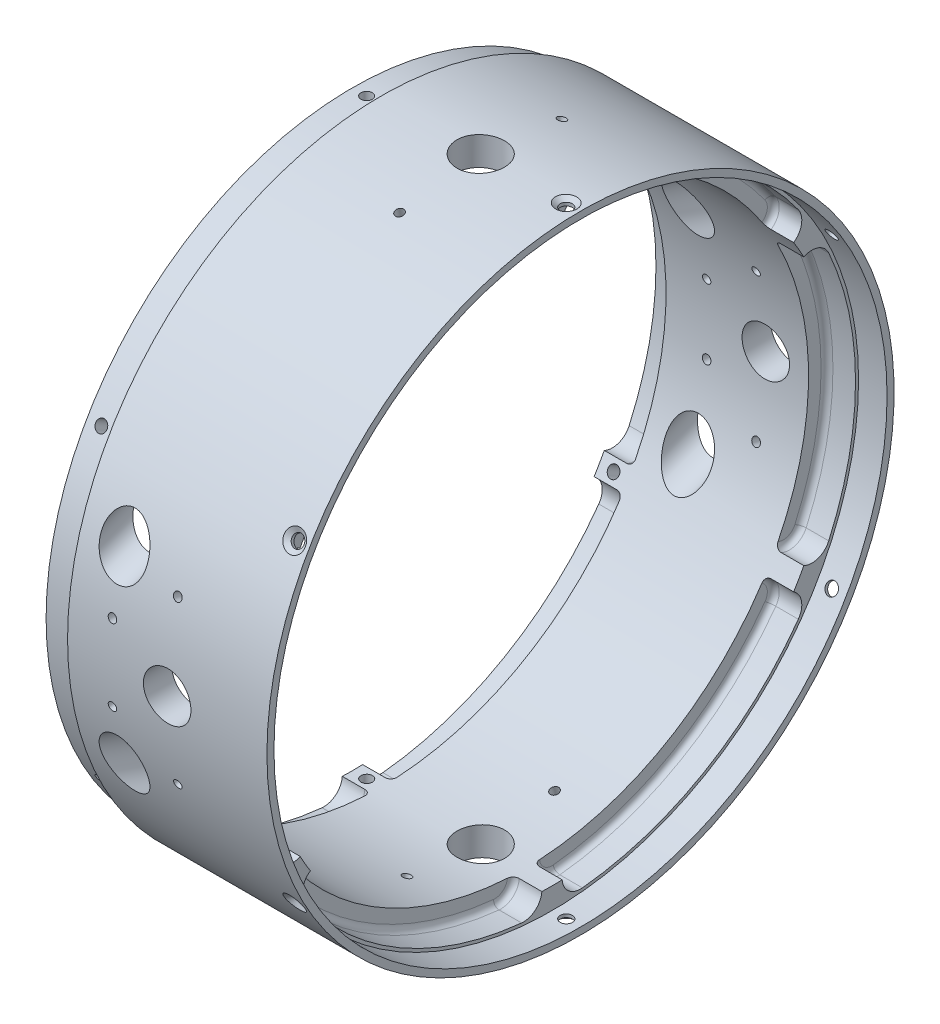
SolidWorks part; units mm, degrees
note: '?' marks a value the reader was unsure of.
material "6061-T6 (SS)"
ref_plane "Front" through (0, 0, 0) normal (0, 0, 1) x (1, 0, 0)
ref_plane "Top" through (0, 0, 0) normal (0, 1, 0) x (1, 0, 0)
ref_plane "Right" through (0, 0, 0) normal (1, 0, 0) x (0, 0, -1)
sketch "Sketch1" plane through (0, 0, 0) normal (0, 0, 1) x (1, 0, 0)
  line L0 (-0.762, 7.62) -> (7.62, 7.62)
  line L1 (-45.6692, 7.62) -> (-0.762, 7.62)
  line L2 (7.62, 7.62) -> (7.62, 5.7404)
  line L3 (0, 0) -> (-53.34, 0)
  line L4 (7.62, 5.7404) -> (0, 5.7404)
  line L5 (-53.34, 5.6896) -> (-53.34, 0)
  line L6 (-45.6692, 7.62) -> (-45.6692, 5.6896)
  line L7 (-45.6692, 5.6896) -> (-53.34, 5.6896)
  line L8 (-51.9562, -76.2) -> (21.757, -76.2) construction
  line L9 (0, 5.7404) -> (0, 0)
  point P1 (-7.62, 0)
  point P4 (-45.72, 0)
  dimension "D1" = 7.6708
  dimension "D2" = 8.382
  dimension "D3" = 1.8796
  dimension "D4" = 7.62
  dimension "D5" = 76.2
  dimension "D6" = 5.6896
  dimension "D7" = 38.1
  dimension "D8" = 83.82
  dimension "D9" = 7.62
  dimension "D10" = 7.62
revolve "Revolve2" add sketch "Sketch1" angle 360 about L8
ref_point "Point1"
ref_plane "Plane1" through (0, -76.2, 0) normal (0, 1, 0) x (1, 0, 0)
ref_plane "Plane2" through (0, -158.0896, 0) normal (0, -1, 0) x (-1, 0, 0)
hole_wizard "#31 (0.12) Diameter Hole1" positions "3DSketch1" profile "Sketch11" hole size "#31" standard "ANSI Inch"
sketch3d "3DSketch1"
  point P0 (-49.53, -158.0896, 0)
  dimension "D1" = 3.81
sketch "Sketch11" plane through (-49.53, -158.0896, 0) normal (1, 0, 0) x (0, 0, -1)
  line L0 (0, 0) -> (0, 185.9821)
  line L1 (0, 185.9821) -> (1.524, 185.9821)
  line L2 (1.524, 185.9821) -> (1.524, 0)
  line L5 (1.524, 0) -> (0, 0)
  line L11 (0, -6.35) -> (0, 107.95) construction
  dimension "Thru Hole Dia." = 3.048
  dimension "Thru Hole Depth" = 185.9821
pattern_circular "CirPattern4" count 6 over 360 of "#31 (0.12) Diameter Hole1"
sketch "Sketch8" plane through (-53.34, 0, 0) normal (-1, 0, 0) x (0, 0, 1)
  line L0 (-7.6343, -152.0166) -> (0, -76.2) construction
  line L1 (0, -76.2) -> (0, -152.4) construction
  line L2 (-61.8419, -120.7198) -> (0, -76.2) construction
  line L3 (0, -76.2) -> (-65.9911, -114.3) construction
  circle A0 centre (0, -76.2) radius 76.2 construction
  arc A1 (-65.841, -123.5988) -> (-8.128, -156.9194) centre (0, -76.2) ccw
  circle A2 centre (0, -76.2) radius 81.8896 construction
  circle A3 centre (0, -76.2) radius 76.2
  arc A4 (-64.5901, -116.6297) -> (-2.7181, -152.3515) centre (0, -76.2) ccw
  circle A5 centre (0, -76.2) radius 81.8896
  circle A6 centre (-61.8419, -120.7198) radius 4.9276
  circle A7 centre (-7.6343, -152.0166) radius 4.9276
  arc A8 (-1.524, -158.0754) -> (1.524, -158.0754) centre (0, -76.2) ccw construction
  arc A9 (-1.524, -152.3848) -> (1.524, -152.3848) centre (0, -76.2) ccw construction
  arc A10 (-1.524, -158.0754) -> (1.524, -158.0754) centre (0, -76.2) ccw
  arc A11 (-1.524, -152.3848) -> (1.524, -152.3848) centre (0, -76.2) ccw
  arc A12 (-64.5901, -116.6297) -> (-2.7181, -152.3515) centre (0, -76.2) ccw
  arc A13 (-66.7399, -112.9726) -> (-65.2159, -115.6122) centre (0, -76.2) ccw construction
  arc A14 (-66.7399, -112.9726) -> (-65.2159, -115.6122) centre (0, -76.2) ccw
  arc A15 (-71.6682, -115.8179) -> (-70.1442, -118.4575) centre (0, -76.2) ccw construction
  arc A16 (-71.6682, -115.8179) -> (-70.1442, -118.4575) centre (0, -76.2) ccw
  point P3 (0, -152.4)
  point P14 (-8.128, -156.9194)
  point P16 (-65.841, -123.5988)
  point P20 (-65.9911, -114.3)
  dimension "D2" = 5.75
  dimension "D3" = 0.762
  dimension "D4" = 5.75
  dimension "D1" = 0
extrude "Cut-Extrude1" cut sketch "Sketch8" against normal blind 7.62
sketch "Sketch13" plane through (0, 0, 0) normal (1, 0, 0) x (0, 0, -1)
  arc A0 (7.1406, -147.1138) -> (8.128, -156.9194) centre (7.6343, -152.0166) ccw
  arc A2 (65.841, -123.5988) -> (57.8428, -117.8409) centre (61.8419, -120.7198) ccw
  arc A4 (8.128, -156.9194) -> (65.841, -123.5988) centre (0, -76.2) ccw
  circle A5 centre (0, -76.2) radius 81.9404 construction
  arc A6 (7.1406, -147.1138) -> (57.8428, -117.8409) centre (0, -76.2) ccw
  arc A7 (2.7181, -152.3515) -> (8.128, -156.9194) centre (7.6343, -152.0166) ccw construction
  arc A8 (65.841, -123.5988) -> (64.5901, -116.6297) centre (61.8419, -120.7198) ccw construction
  circle M12 centre (0, -76.2) radius 76.2
extrude "Cut-Extrude2" cut sketch "Sketch13" against normal blind 7.62 contours A0 A4 A2 M12
fillet "Fillet1" radius 1.5875 6 edges at (-45.72, -155.7816, -4.4553) (-45.72, -146.4586, -40.5638) (-45.72, -119.8492, -66.692) (-7.62, -155.7816, -4.4553) (-7.62, -119.8492, -66.692) (-7.62, -146.4586, -40.5638)
pattern_circular "CirPattern3" count 6 over 360 about axis through (0, -76.2, 0) along (1, 0, 0) of "Cut-Extrude2", "Cut-Extrude1", "Fillet1"
hole_wizard "CSK for #4 Flat Head Machine Screw (100)1" positions "3DSketch5" profile "Sketch18" countersink size "#4" standard "ANSI Inch" end condition through all
sketch3d "3DSketch5"
  line L1 (3.81, -160.02, 0) -> (7.62, -160.02, 0) construction
  circle A0 centre (7.62, -76.2, 0) radius 83.82 construction
  point P0 (3.81, -160.02, 0)
  point P8 (-76.2, -76.2, 0)
  dimension "D1" = 3.81
sketch "Sketch18" plane through (3.81, -160.02, 0) normal (1, 0, 0) x (0, 0, -1)
  line L0 (0, 0) -> (0, 198.3202)
  line L1 (0, 198.3202) -> (1.6319, 198.3202)
  line L2 (1.6319, 198.3202) -> (1.6319, 1.0284)
  line L3 (1.6319, 1.0284) -> (2.8575, 0)
  line L5 (2.8575, 0) -> (0, 0)
  line L6 (-1.6319, 1.0284) -> (-2.8575, 0) construction
  line L11 (0, -6.35) -> (0, 107.95) construction
  dimension "Thru Hole Dia." = 3.2639
  dimension "Thru Hole Depth" = 198.3202
  dimension "Near C'Sink Dia." = 5.715
  dimension "Near C'Sink Angle" = 100
pattern_circular "CirPattern5" count 6 over 360 of "CSK for #4 Flat Head Machine Screw (100)1"
ref_axis "Axis1" through (0, -76.2, 0) along (-1, 0, 0)?
ref_plane "Plane3" [suppressed] through (0, -38.1, -38.1) normal (0, 0.7071, 0.7071) x (1, 0, 0)
sketch "Sketch19" [suppressed] plane through (0, 0, 0) normal (0, 0, 1) x (1, 0, 0)
  line L0 (-66.04, -76.2) -> (7.62, -76.2) construction
  line L1 (-66.04, 5.6896) -> (-66.04, -158.0896) construction
  line L2 (7.62, -160.02) -> (7.62, 7.62) construction
  line L3 (-58.3692, 7.62) -> (-58.3692, -160.02) construction
  circle A0 centre (-44.3992, -127) radius 6.35
  dimension "D1" = 12.7
  dimension "D2" = 50.8
  dimension "D3" = 13.97
extrude "Cut-Extrude3" [suppressed] cut sketch "Sketch19" against normal up to next
sketch "Sketch20" [suppressed] plane through (0, -38.1, -38.1) normal (0, 0.7071, 0.7071) x (1, 0, 0)
  line L0 (-66.04, -53.8815) -> (7.62, -53.8815) construction
  line L1 (-66.04, 28.0081) -> (-66.04, -135.7711) construction
  line L2 (7.62, -137.7015) -> (7.62, 29.9385) construction
  line L3 (-58.3692, 29.9385) -> (-58.3692, -137.7015) construction
  circle A0 centre (-44.3992, -3.0815) radius 6.35
  dimension "D1" = 12.7
  dimension "D2" = 50.8
  dimension "D3" = 13.97
extrude "Cut-Extrude4" [suppressed] cut sketch "Sketch20" against normal up to next
sketch "Sketch21" plane through (0, 0, 0) normal (0, 0, 1) x (1, 0, 0)
  line L0 (-53.34, -76.2) -> (7.62, -76.2) construction
  line L1 (-53.34, 5.6896) -> (-53.34, -158.0896) construction
  line L2 (7.62, -160.02) -> (7.62, 7.62) construction
  circle A0 centre (-19.05, -76.2) radius 6.35
  dimension "D1" = 12.7
  dimension "D2" = 26.67
extrude "Cut-Extrude6" cut sketch "Sketch21" against normal up to next
pattern_circular "CirPattern6" count 4 over 360 of "Cut-Extrude6"
ref_axis "Axis2" through (-19.05, -76.2, -83.82) along (0, 0, 1)?
ref_plane "Plane4" through (0, -76.2, 0) normal (0, -1, 0) x (-1, 0, 0)
ref_plane "Plane5" through (0, -8.9137, -24.4902) normal (0, 0.342, 0.9397) x (-1, 0, 0)
ref_plane "Plane6" through (0, -8.9137, 24.4902) normal (0, 0.342, -0.9397) x (-1, 0, 0)
sketch "Sketch22" plane through (0, -8.9137, 24.4902) normal (0, 0.342, -0.9397) x (-1, 0, 0)
  line L0 (-7.62, -71.6046) -> (53.34, -71.6046) construction
  line L1 (-7.62, 12.2154) -> (-7.62, -155.4246) construction
  line L2 (53.34, -153.4942) -> (53.34, 10.285) construction
  line L4 (7.62, -132.6508) -> (7.62, -147.8046) construction
  circle A0 centre (34.29, -122.4046) radius 6.35
  dimension "D1" = 12.7
  dimension "D2" = 50.8
  dimension "D3" = 26.67
extrude "Cut-Extrude7" cut sketch "Sketch22" along normal up to next contours A0
mirror "Mirror1" about plane through (0, -76.2, 0) normal (0, 1, 0) of "Cut-Extrude7"
mirror "Mirror2" about plane through (0, 0, 0) normal (0, 0, 1) of "Mirror1", "Cut-Extrude7"
ref_axis "Axis3" through (-19.05, 7.62, 0) along (0, -1, 0)?
hole_wizard "#4-40 Tapped Hole1" positions "3DSketch10" profile "Sketch26" tap size "#4-40" standard "ANSI Inch"
sketch3d "3DSketch10"
  line L2 (0, -76.2, 0) -> (-53.34, -76.2, 0) construction
  line L3 (-19.05, 7.62, 0) -> (-19.05, -159.4754, 0) construction
  line L4 (-19.05, -56.478, -73.6035) -> (-19.05, -95.922, 73.6035) construction
  line L6 (-19.05, -95.922, -73.6035) -> (-19.05, -56.478, 73.6035) construction
  line L8 (-19.05, -2.5965, -19.722) -> (-19.05, -149.8035, 19.722) construction
  line L9 (-19.05, -149.8035, -19.722) -> (-19.05, -2.5965, 19.722) construction
  line L11 (-19.05, -76.2, -83.82) -> (-19.05, -76.2, 88.2257) construction
  circle A0 centre (-19.05, -76.2, 0) radius 76.2
  point P3 (57.15, -76.2, 0)
  point P31 (-19.05, -95.922, 73.6035)
  point P33 (-19.05, -56.478, 73.6035)
  point P42 (-19.05, -2.5965, 19.722)
  point P44 (-19.05, -2.5965, -19.722)
  point P51 (-19.05, -56.478, -73.6035)
  point P53 (-19.05, -95.922, -73.6035)
  point P55 (-19.05, -149.8035, -19.722)
  point P57 (-19.05, -149.8035, 19.722)
  point P77 (-19.05, -76.2, 0)
  dimension "D1" = 15
  dimension "D3" = 15
  dimension "D2" = 15
  dimension "D4" = 15
sketch "Sketch26" plane through (-19.05, -95.922, 73.6035) normal (1, 0, 0) x (0, 0.9659, 0.2588)
  line L0 (0, 0) -> (0, 9.5438)
  line L1 (0, 9.5438) -> (1.1303, 8.8646)
  line L2 (1.1303, 8.8646) -> (1.1303, 0)
  line L5 (1.1303, 0) -> (0, 0)
  line L10 (0, 9.5438) -> (-1.1303, 8.8646) construction
  line L11 (0, -6.35) -> (0, 107.95) construction
  dimension "Tap Drill Dia." = 2.2606
  dimension "Tap Drill Depth" = 8.8646
  dimension "Drill Angle" = 118
cosmetic thread "Hole Thread1" parameters "D1"=5.6896, "D2"=2.8448
cosmetic thread "Hole Thread2" parameters "D1"=5.6896, "D2"=2.8448
cosmetic thread "Hole Thread3" parameters "D1"=5.6896, "D2"=2.8448
cosmetic thread "Hole Thread4" parameters "D1"=5.6896, "D2"=2.8448
cosmetic thread "Hole Thread5" parameters "D1"=5.6896, "D2"=2.8448
cosmetic thread "Hole Thread6" parameters "D1"=5.6896, "D2"=2.8448
cosmetic thread "Hole Thread7" parameters "D1"=5.6896, "D2"=2.8448
cosmetic thread "Hole Thread8" parameters "D1"=5.6896, "D2"=2.8448
sketch3d "3DSketch2"
  circle A0 centre (-24.9799, -157.9493, -0.0042) radius 2.0193
  point P2 (-24.9799, -155.93, -0.0042)
  dimension "D1" = 4.0386
hole_wizard "#4-40 Tapped Hole2" positions "3DSketch11" profile "Sketch27" tap size "#4-40" standard "ANSI Inch"
sketch3d "3DSketch11"
  circle A0 centre (-34.29, -84.7303, 69.4733) radius 1.6319 construction
  circle A1 centre (-34.29, -67.6697, 69.4733) radius 1.6319 construction
  circle A2 centre (-34.2899, -84.7303, -69.4733) radius 1.6319 construction
  circle A3 centre (-34.2901, -67.6697, -69.4733) radius 1.6319 construction
  point P0 (-34.2901, -66.9136, -75.632)
  point P2 (-34.2899, -85.4864, -75.632)
  point P4 (-34.29, -66.9136, 75.632)
  point P6 (-34.29, -85.4864, 75.632)
  point P12 (-34.29, -84.5314, 67.8535)
  point P15 (-34.29, -67.8686, 67.8535)
  point P18 (-34.2899, -84.5314, -67.8535)
  point P22 (-34.2901, -67.8686, -67.8535)
sketch "Sketch27" plane through (-34.2901, -66.9136, -75.632) normal (1, 0, 0) x (0, -0.9925, -0.1219)
  line L0 (0, 0) -> (0, 9.5438)
  line L1 (0, 9.5438) -> (1.1303, 8.8646)
  line L2 (1.1303, 8.8646) -> (1.1303, 0)
  line L5 (1.1303, 0) -> (0, 0)
  line L10 (0, 9.5438) -> (-1.1303, 8.8646) construction
  line L11 (0, -6.35) -> (0, 107.95) construction
  dimension "Tap Drill Dia." = 2.2606
  dimension "Tap Drill Depth" = 8.8646
  dimension "Drill Angle" = 118
cosmetic thread "Hole Thread9" parameters "D1"=5.6896, "D2"=2.8448
cosmetic thread "Hole Thread10" parameters "D1"=5.6896, "D2"=2.8448
cosmetic thread "Hole Thread11" parameters "D1"=5.6896, "D2"=2.8448
cosmetic thread "Hole Thread12" parameters "D1"=5.6896, "D2"=2.8448
